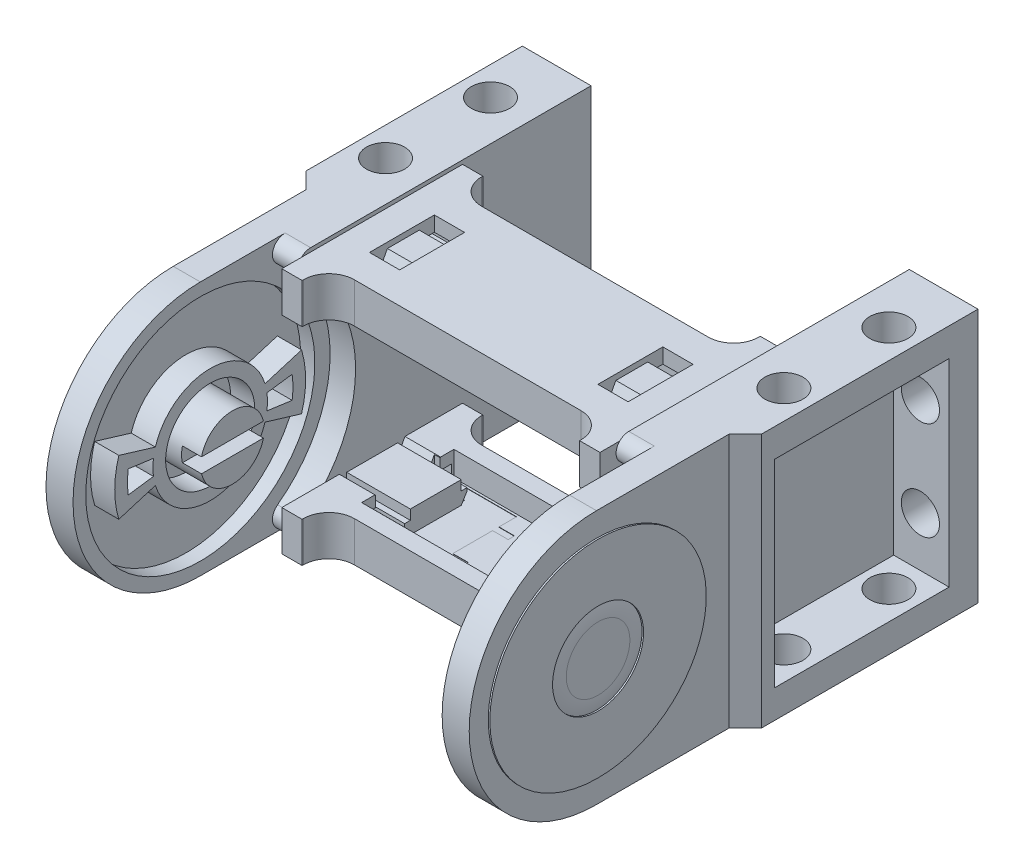
SolidWorks part; units mm, degrees
material "ABS"
ref_plane "Front Plane" through (0, 0, 0) normal (0, 0, 1) x (1, 0, 0)
ref_plane "Top Plane" through (0, 0, 0) normal (0, 1, 0) x (1, 0, 0)
ref_plane "Right Plane" through (0, 0, 0) normal (1, 0, 0) x (0, 0, -1)
other "Configuration Table"
ref_plane "Plane1" through (31.25, 0, 0) normal (1, 0, 0) x (0, 0, -1)
sketch "Sketch1" plane through (31.25, 0, 0) normal (1, 0, 0) x (0, 0, -1)
  line L0 (0, 0) -> (46, 0) construction
  line L1 (0, 20) -> (30.5828, 20)
  line L2 (0, -20) -> (30.5828, -20)
  line L3 (46, 20) -> (46, -20) construction
  arc A0 (0, 20) -> (0, -20) centre (0, 0) ccw
  circle A2 centre (0, 0) radius 5
  arc A7 (31.8838, 16.481) -> (31.8838, -16.481) centre (46, 0) ccw
  arc A8 (30.5828, -20) -> (31.8838, -16.481) centre (30.5828, -18) ccw
  arc A9 (31.8838, 16.481) -> (30.5828, 20) centre (30.5828, 18) ccw
  point P6 (0, 0)
  point P8 (0, 0)
  point P12 (61.1075, 20)
  dimension "D2" = 40
  dimension "D3" = 10
  dimension "D4" = 21.7
  dimension "D5" = 2
  dimension "D1" = 46
extrude "Boss-Extrude1" add sketch "Sketch1" along normal blind 2
sketch "Sketch2" plane through (33.25, 0, 0) normal (1, 0, 0) x (0, 0, -1)
  circle A0 centre (0, 0) radius 7.15
  ellipse E0 centre (0, 0) end of major axis (-17, 0) minor radius 16.25
  dimension "D3" = 14.3
  dimension "D1" = 34
  dimension "D2" = 32.5
extrude "Boss-Extrude2" add sketch "Sketch2" along normal blind 0.25
sketch "Sketch3" plane through (31.25, 0, 0) normal (-1, 0, 0) x (0, 0, 1)
  line L4 (-30.5828, -20) -> (0, -20)
  line L5 (0, 20) -> (-30.5828, 20)
  line L6 (-30.5828, -20) -> (0, -20)
  line L7 (0, 20) -> (-30.5828, 20)
  circle A4 centre (0, 0) radius 18
  arc A8 (-30.5828, 20) -> (-31.8838, 16.481) centre (-30.5828, 18) ccw
  arc A9 (0, -20) -> (0, 20) centre (0, 0) ccw
  arc A10 (-30.5828, 20) -> (-31.8838, 16.481) centre (-30.5828, 18) ccw
  arc A11 (-31.8838, -16.481) -> (-31.8838, 16.481) centre (-46, 0) ccw
  arc A13 (0, -20) -> (0, 20) centre (0, 0) ccw
  arc A17 (-31.8838, -16.481) -> (-31.8838, 16.481) centre (-46, 0) ccw
  arc A18 (-31.8838, -16.481) -> (-30.5828, -20) centre (-30.5828, -18) ccw
  arc A19 (-31.8838, -16.481) -> (-30.5828, -20) centre (-30.5828, -18) ccw
  dimension "D2" = 2
  dimension "D1" = 0
extrude "Boss-Extrude3" add sketch "Sketch3" along normal blind 2.25
sketch "Sketch5" plane through (31.25, 0, 0) normal (-1, 0, 0) x (0, 0, 1)
  line L0 (-20.8019, 0) -> (21.6225, 0) construction
  line L1 (-12.8779, 1.7773) -> (-8.9155, 1.2305)
  line L2 (-8.6132, 2.61) -> (-14.3554, 4.35)
  line L3 (-8.9155, 1.2305) -> (0, 0) construction
  line L4 (-8.6132, 2.61) -> (0, 0) construction
  line L5 (-8.6132, -2.61) -> (-14.3554, -4.35)
  line L6 (-12.8779, -1.7773) -> (-8.9155, -1.2305)
  line L7 (0, -21.0754) -> (0, 22.5568) construction
  line L8 (12.8779, -1.7773) -> (8.9155, -1.2305)
  line L9 (8.6132, -2.61) -> (14.3554, -4.35)
  line L10 (8.6132, 2.61) -> (14.3554, 4.35)
  line L11 (12.8779, 1.7773) -> (8.9155, 1.2305)
  arc A0 (-8.9155, 1.2305) -> (-8.9155, -1.2305) centre (0, 0) ccw
  circle A1 centre (0, 0) radius 7
  arc A2 (-14.3554, 4.35) -> (-14.3554, -4.35) centre (0, 0) ccw
  arc A3 (-12.8779, 1.7773) -> (-12.8779, -1.7773) centre (0, 0) ccw
  arc A4 (-8.6132, -2.61) -> (8.6132, -2.61) centre (0, 0) ccw
  arc A5 (12.8779, 1.7773) -> (12.8779, -1.7773) centre (0, 0) cw
  arc A6 (14.3554, 4.35) -> (14.3554, -4.35) centre (0, 0) cw
  arc A7 (8.6132, 2.61) -> (-8.6132, 2.61) centre (0, 0) ccw
  arc A8 (8.9155, -1.2305) -> (8.9155, 1.2305) centre (0, 0) ccw
  dimension "D1" = 14
  dimension "D2" = 18
  dimension "D3" = 26
  dimension "D4" = 30
  dimension "D5" = 9
  dimension "D6" = 8.7
extrude "Boss-Extrude4" add sketch "Sketch5" along normal blind 3.8
sketch "Sketch6" plane through (29, 0, 0) normal (1, 0, 0) x (0, 0, -1)
  line L0 (13.3327, 20) -> (57.4, 20)
  line L1 (13.3327, -20) -> (57.4, -20)
  line L2 (57.4, 0) -> (0, 0) construction
  line L3 (30.5828, 20) -> (0, 20) construction
  line L4 (0, -20) -> (30.5828, -20) construction
  line L5 (-20, 0) -> (0, 0) construction
  line L6 (57.4, -20) -> (57.4, 20)
  arc A2 (12.1422, -16.3929) -> (12.1422, 16.3929) centre (0, 0) ccw
  arc A3 (13.3327, -20) -> (12.1422, -16.3929) centre (13.3327, -18) cw
  arc A4 (13.3327, 20) -> (12.1422, 16.3929) centre (13.3327, 18) ccw
  arc A11 (0, 20) -> (0, -20) centre (0, 0) ccw construction
  point P19 (4.02, -20)
  point P22 (4.02, 20)
  dimension "D2" = 40.4
  dimension "D3" = 2
  dimension "D1" = 77.4
extrude "Boss-Extrude5" add sketch "Sketch6" against normal blind 4
extrude "Boss-Extrude11" add sketch "Эскиз6<2>" along normal up to surface (4.25 mm away) up to face at (33.25, 0, -5)
sketch "Эскиз6<2>" plane through (29, 0, 0) normal (1, 0, 0) x (0, 0, -1) same geometry as "Sketch6"
sketch "Sketch25" plane through (0, -20, 0) normal (0, -1, 0) x (1, 0, 0)
  line L5 (33.25, 0) -> (33.25, -57.4) construction
  line L6 (33.25, -57.4) -> (35.8, -57.4)
  line L7 (35.8, -57.4) -> (35.8, -23.4)
  line L8 (35.8, -23.4) -> (33.25, -20.85)
  line L9 (33.25, -20.85) -> (33.25, -57.4)
  line L10 (25, -13.3327) -> (25, -57.4) construction
  line L11 (25, -57.4) -> (33.25, -57.4) construction
  dimension "D1" = 10.8
  dimension "D4" = 34
  dimension "D5" = 135
extrude "Boss-Extrude12" add sketch "Sketch25" against normal up to surface (40 mm away) up to face at (29.0833, 20, -23.5776)
sketch "Sketch26" plane through (35.8, 0, 0) normal (1, 0, 0) x (0, 0, -1)
  line L0 (57.4, 20) -> (57.4, -20) construction
  line L1 (25.45, 15.55) -> (52.85, 15.55)
  line L2 (25.45, 15.55) -> (25.45, -15.55)
  line L3 (25.45, -15.55) -> (52.85, -15.55)
  line L4 (52.85, 15.55) -> (52.85, -15.55)
  line L5 (57.4, -20) -> (23.4, -20) construction
  line L6 (23.4, 20) -> (57.4, 20) construction
  dimension "D1" = 4.55
  dimension "D2" = 4.45
  dimension "D3" = 4.45
  dimension "D4" = 27.4
extrude "Cut-Extrude8" cut sketch "Sketch26" against normal blind 8.7
sketch "Sketch28" plane through (0, 20, 0) normal (0, 1, 0) x (1, 0, 0)
  line L0 (35.8, 23.4) -> (35.8, 57.4) construction
  line L1 (25, 57.4) -> (35.8, 57.4) construction
  circle A0 centre (31.3, 47.9) radius 3
  circle A1 centre (31.3, 31.4) radius 3
  dimension "D1" = 6
  dimension "D2" = 4.5
  dimension "D3" = 9.5
  dimension "D4" = 16.5
extrude "Cut-Extrude9" cut sketch "Sketch28" against normal through all
sketch "Sketch29" plane through (0, 0, -57.4) normal (0, 0, -1) x (-1, 0, 0)
  line L0 (-31.3, 20) -> (-31.3, -20) construction
  line L1 (-25, 20) -> (-35.8, 20) construction
  line L2 (-35.8, 0) -> (-25, 0) construction
  line L3 (-35.8, 20) -> (-35.8, -20) construction
  line L4 (-25, -20) -> (-25, 20) construction
  line L5 (-25, -20) -> (-35.8, -20) construction
  circle A0 centre (-31.3, 7.75) radius 3
  circle A1 centre (-31.3, -7.75) radius 3
  dimension "D1" = 6
  dimension "D4" = 9.5
  dimension "D5" = 21.5
  dimension "D2" = 15.5
  dimension "D3" = 4.5
extrude "Cut-Extrude10" cut sketch "Sketch29" against normal up to next
sketch "Sketch11" plane through (25, 0, 0) normal (-1, 0, 0) x (0, 0, 1)
  line L0 (-23, 0) -> (-23, 20) construction
  line L1 (-20.85, 20) -> (-23.4, 20) construction
  line L3 (-46, 0) -> (0, 0) construction
  line L4 (-27, 13.4) -> (-27, 14.94)
  line L5 (-27, 13.4) -> (-19, 13.4)
  line L6 (-27, 14.94) -> (-27.9, 14.94)
  line L7 (-27.9, 14.94) -> (-27.9, 15.44)
  line L8 (-27.9, 15.44) -> (-27, 16.9)
  line L9 (-27, 16.9) -> (-19, 16.9)
  line L10 (-18.1, 15.44) -> (-19, 16.9)
  line L11 (-18.1, 14.94) -> (-18.1, 15.44)
  line L12 (-19, 14.94) -> (-18.1, 14.94)
  line L13 (-19, 13.4) -> (-19, 14.94)
  line L14 (-19, -13.4) -> (-19, -14.94)
  line L15 (-19, -14.94) -> (-18.1, -14.94)
  line L16 (-18.1, -14.94) -> (-18.1, -15.44)
  line L17 (-18.1, -15.44) -> (-19, -16.9)
  line L18 (-27, -16.9) -> (-19, -16.9)
  line L19 (-27.9, -15.44) -> (-27, -16.9)
  line L20 (-27.9, -14.94) -> (-27.9, -15.44)
  line L21 (-27, -14.94) -> (-27.9, -14.94)
  line L22 (-27, -13.4) -> (-19, -13.4)
  line L23 (-27, -13.4) -> (-27, -14.94)
  point P5 (0, 0)
  dimension "D1" = 1.54
  dimension "D2" = 26.8
  dimension "D3" = 33.8
  dimension "D4" = 8
  dimension "D5" = 9.8
  dimension "D6" = 0.5
  dimension "D7" = 46
extrude "Boss-Extrude8" add sketch "Sketch11" along normal blind 10
sketch "Sketch13" plane through (0, 16.9, 0) normal (0, 1, 0) x (1, 0, 0)
  line L0 (15.8, 30.3851) -> (15.8, 15.9317) construction
  line L1 (15, 19) -> (15, 27) construction
  dimension "D1" = 0.8
ref_plane "Plane2" through (15.8, 0, 0) normal (-1, 0, 0) x (0, 0, 1)
sketch "Sketch15" plane through (15.8, 0, 0) normal (-1, 0, 0) x (0, 0, 1)
  line L0 (-23, 13.4) -> (-23, 20.5432) construction
  line L1 (-27, 13.4) -> (-19, 13.4) construction
  line L2 (-25.5, 18.75) -> (-20.5, 18.75)
  line L3 (-20.5, 18.75) -> (-19.5, 16.9)
  line L4 (-30.3851, 16.9) -> (-15.9317, 16.9) construction
  line L5 (-19.5, 16.9) -> (-26.5, 16.9)
  line L6 (-25.5, 18.75) -> (-26.5, 16.9)
  line L7 (-57.4, 20) -> (-13.3327, 20) construction
  dimension "D1" = 7
  dimension "D2" = 5
  dimension "D3" = 1.85
  dimension "D4" = 1.25
extrude "Boss-Extrude9" add sketch "Sketch15" against normal blind 4.3
mirror "Mirror1" about plane through (0, 0, 0) normal (0, 1, 0) of "Boss-Extrude9"
mirror "Mirror2" about plane through (0, 0, 0) normal (1, 0, 0) of bodies 114
ref_plane "Plane3" through (0, 19.4, 0) normal (0, 1, 0) x (1, 0, 0)
sketch "Sketch17" plane through (0, 19.4, 0) normal (0, 1, 0) x (1, 0, 0)
  line L0 (0, 0) -> (0, 46) construction
  line L1 (-25, 23) -> (25, 23) construction
  line L2 (-25, 19) -> (-25, 27) construction
  line L3 (25, 19) -> (25, 27) construction
  line L4 (21.8, 9) -> (21.8, 8.8)
  line L5 (17.8, 13) -> (-17.8, 13)
  line L7 (17.8, 33) -> (-17.8, 33)
  line L9 (21.8, 13) -> (-21.8, 33) construction
  line L10 (21.8, 33) -> (-21.8, 13) construction
  line L11 (21.8, 37.2) -> (25, 37.2)
  line L12 (21.8, 37.2) -> (21.8, 37)
  line L13 (21.8, 8.8) -> (25, 8.8)
  line L14 (25, 37.2) -> (25, 8.8)
  line L15 (-25, 37.2) -> (-25, 8.8)
  line L16 (-21.8, 8.8) -> (-25, 8.8)
  line L17 (-21.8, 37.2) -> (-21.8, 37)
  line L18 (-21.8, 37.2) -> (-25, 37.2)
  line L19 (-21.8, 9) -> (-21.8, 8.8)
  line L20 (-15.8, 25.5) -> (-20.1, 20.5) construction
  line L21 (20.325, 17.9) -> (15.575, 17.9)
  line L22 (-20.325, 17.9) -> (-15.575, 17.9)
  line L23 (-20.325, 17.9) -> (-20.325, 28.1)
  line L24 (-20.325, 28.1) -> (-15.575, 28.1)
  line L25 (-15.575, 17.9) -> (-15.575, 28.1)
  line L26 (-20.325, 17.9) -> (-15.575, 28.1) construction
  line L27 (-20.325, 28.1) -> (-15.575, 17.9) construction
  line L28 (15.575, 17.9) -> (15.575, 28.1)
  line L29 (20.325, 17.9) -> (20.325, 28.1)
  line L30 (20.325, 28.1) -> (15.575, 28.1)
  arc A0 (21.8, 37) -> (17.8, 33) centre (17.8, 37) cw
  arc A1 (17.8, 13) -> (21.8, 9) centre (17.8, 9) cw
  arc A2 (-17.8, 13) -> (-21.8, 9) centre (-17.8, 9) ccw
  arc A3 (-17.8, 33) -> (-21.8, 37) centre (-17.8, 37) cw
  point P4 (0, 23)
  point P10 (0, 23)
  point P39 (-17.95, 23)
  point P40 (-17.95, 23)
  dimension "D5" = 4
  dimension "D1" = 28.4
  dimension "D2" = 3.2
  dimension "D3" = 20
  dimension "D4" = 50
  dimension "D6" = 10.2
  dimension "D7" = 4.75
extrude "Boss-Extrude10" add sketch "Sketch17" against normal blind 6.3 separate body
sketch "Sketch18" plane through (25, 0, 0) normal (1, 0, 0) x (0, 0, -1)
  line L0 (23, 13.1) -> (23, 19.4) construction
  line L1 (8.8, 13.1) -> (37.2, 13.1) construction
  line L2 (4.5375, 19.4) -> (-4.5375, 19.4) construction
  line L4 (29.89, 14.9) -> (16.11, 14.9)
  line L5 (29.89, 14.9) -> (29.89, 17.05)
  line L6 (29.89, 17.05) -> (16.11, 17.05)
  line L7 (16.11, 14.9) -> (16.11, 17.05)
  line L8 (29.89, 14.9) -> (16.11, 17.05) construction
  line L9 (29.89, 17.05) -> (16.11, 14.9) construction
  point P6 (23, 15.975)
  dimension "D1" = 13.78
  dimension "D2" = 2.15
  dimension "D3" = 2.35
extrude "Cut-Extrude3" cut sketch "Sketch18" against normal blind 15.8
sketch "Sketch19" plane through (25, 0, 0) normal (1, 0, 0) x (0, 0, -1)
  line L0 (23, 14.9) -> (23, 13.1) construction
  line L1 (16.11, 14.9) -> (29.89, 14.9) construction
  line L2 (8.8, 13.1) -> (37.2, 13.1) construction
  line L3 (18.8, 14.9) -> (17.85, 13.1)
  line L4 (17.85, 13.1) -> (28.15, 13.1)
  line L5 (28.15, 13.1) -> (27.2, 14.9)
  line L6 (27.2, 14.9) -> (18.8, 14.9)
  dimension "D1" = 10.3
  dimension "D2" = 8.4
extrude "Cut-Extrude4" cut sketch "Sketch19" against normal blind 11.25
sketch "Sketch20" plane through (0, 13.1, 0) normal (0, -1, 0) x (1, 0, 0)
  line L0 (13.75, -23) -> (13.5581, -23) construction
  line L1 (13.75, -17.85) -> (13.75, -28.15) construction
  line L2 (6.75, -27.125) -> (6.75, -26.125)
  line L3 (13.75, -18.875) -> (6.75, -18.875)
  line L4 (13.75, -18.875) -> (13.75, -19.875)
  line L5 (13.75, -19.875) -> (6.75, -19.875)
  line L6 (6.75, -18.875) -> (6.75, -19.875)
  line L7 (13.75, -26.125) -> (6.75, -26.125)
  line L8 (13.75, -27.125) -> (13.75, -26.125)
  line L9 (13.75, -27.125) -> (6.75, -27.125)
  dimension "D1" = 6.25
  dimension "D2" = 8.25
  dimension "D3" = 7
extrude "Cut-Extrude5" cut sketch "Sketch20" against normal up to surface (3.95 mm away) up to face at (17.1, 17.05, -23)
mirror "Mirror5" about plane through (0, 0, 0) normal (1, 0, 0) of "Cut-Extrude5", "Cut-Extrude4", "Cut-Extrude3"
sketch "Sketch21" plane through (0, 13.1, 0) normal (0, -1, 0) x (1, 0, 0)
  line L0 (0, -13) -> (0, -33) construction
  line L1 (-17.8, -13) -> (17.8, -13) construction
  line L2 (17.8, -33) -> (-17.8, -33) construction
  line L4 (19.4, -30.25) -> (-19.4, -30.25)
  line L5 (19.4, -30.25) -> (19.4, -15.75)
  line L6 (19.4, -15.75) -> (-19.4, -15.75)
  line L7 (-19.4, -30.25) -> (-19.4, -15.75)
  line L8 (19.4, -30.25) -> (-19.4, -15.75) construction
  line L9 (19.4, -15.75) -> (-19.4, -30.25) construction
  point P6 (0, -23)
  dimension "D1" = 38.8
  dimension "D2" = 14.5
extrude "Cut-Extrude6" cut sketch "Sketch21" against normal blind 3.9
mirror "Mirror4" about plane through (0, 0, 0) normal (0, 1, 0) of bodies 122 116
sketch "Sketch23" plane through (0, 0, 0) normal (0, 1, 0) x (1, 0, 0)
  line L0 (-23.95, 0) -> (-33.5, 0)
  line L2 (-33.5, 17) -> (-33.5, -17) construction
  line L3 (-33.5, 0) -> (-33.5, 5)
  line L4 (-33.25, 20.85) -> (-33.25, 0) construction
  line L5 (-33.25, 5) -> (-23.95, 5)
  line L6 (-23.95, 5) -> (-23.95, 0)
  line L7 (-33.25, 7.2) -> (-33.25, 5)
  arc A0 (-33.5, 5) -> (-33.25, 7.2) centre (-23.695, 5) cw
  dimension "D1" = 7.2
  dimension "D2" = 9.55
  dimension "D3" = 5
revolve "Revolve1" add sketch "Sketch23" angle 360 about L0
sketch "Sketch24" plane through (-23.95, 0, 0) normal (1, 0, 0) x (0, 0, -1)
  line L1 (5, -1.15) -> (-5, -1.15)
  line L2 (5, -1.15) -> (5, 1.15)
  line L3 (5, 1.15) -> (-5, 1.15)
  line L4 (-5, -1.15) -> (-5, 1.15)
  line L5 (5, -1.15) -> (-5, 1.15) construction
  line L6 (5, 1.15) -> (-5, -1.15) construction
  circle A0 centre (0, 0) radius 5 construction
  point P0 (0, 0)
  dimension "D1" = 2.3
extrude "Cut-Extrude7" cut sketch "Sketch24" against normal blind 3
mirror "Mirror6" about plane through (0, 0, 0) normal (1, 0, 0) of bodies 125 123
equation "\"D3@Sketch26\"=\"D2@Sketch26\""
